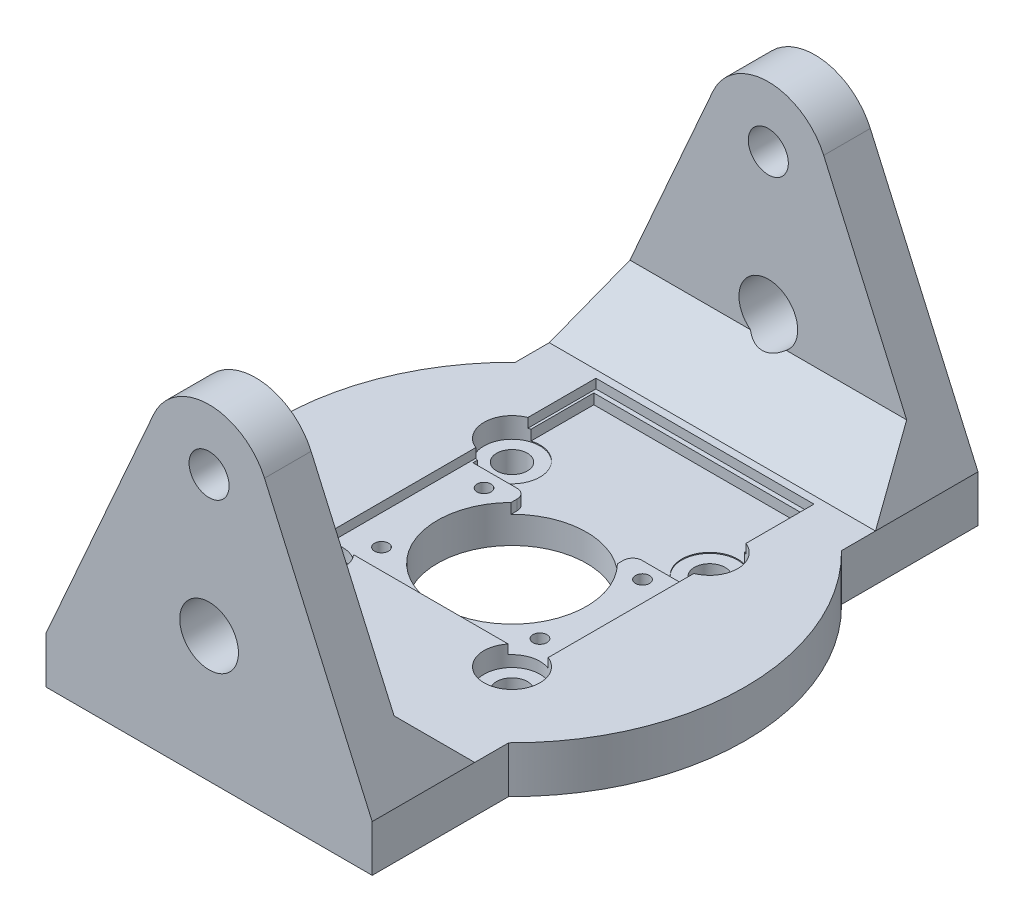
SolidWorks part; units mm, degrees
ref_plane "前视基准面" through (0, 0, 0) normal (0, 0, 1) x (1, 0, 0)
ref_plane "上视基准面" through (0, 0, 0) normal (0, 1, 0) x (1, 0, 0)
ref_plane "右视基准面" through (0, 0, 0) normal (1, 0, 0) x (0, 0, -1)
sketch "草图1" plane through (0, 0, 0) normal (0, 1, 0) x (1, 0, 0)
  line L1 (10.6066, 10.6066) -> (-10.6066, 10.6066) construction
  line L2 (-10.6066, 10.6066) -> (-10.6066, -10.6066) construction
  line L3 (-10.6066, -10.6066) -> (10.6066, -10.6066) construction
  line L4 (10.6066, -10.6066) -> (10.6066, 10.6066) construction
  circle A0 centre (0, 0) radius 25
  circle A1 centre (0, 0) radius 8
  circle A2 centre (0, 0) radius 15 construction
  circle A3 centre (10.6066, 10.6066) radius 1.65
  circle A4 centre (-10.6066, 10.6066) radius 1.65
  circle A5 centre (-10.6066, -10.6066) radius 1.65
  circle A6 centre (10.6066, -10.6066) radius 1.65
  dimension "D1" = 50
  dimension "D2" = 16
  dimension "D3" = 3.3
  dimension "D4" = 30
extrude "凸台-拉伸1" add sketch "草图1" along normal blind 5
sketch "草图5" plane through (0, 5, 0) normal (0, 1, 0) x (1, 0, 0)
  line L0 (11.7, 20.7) -> (-11.7, 20.7)
  line L1 (11, -8) -> (-11, -8) construction
  line L2 (11, -8) -> (11, 20) construction
  line L3 (11, 20) -> (-11, 20) construction
  line L4 (-11, -8) -> (-11, 20) construction
  line L5 (11, -8) -> (-11, 20) construction
  line L6 (11, 20) -> (-11, -8) construction
  line L7 (-11.7, -8.7) -> (-11.7, 20.7)
  line L8 (11.7, -8.7) -> (-11.7, -8.7)
  line L9 (11.7, -8.7) -> (11.7, 20.7)
  line L11 (-8.5, -5.5) -> (8.5, -5.5) construction
  line L12 (-8.5, -5.5) -> (-8.5, 5.5) construction
  line L13 (-8.5, 5.5) -> (8.5, 5.5) construction
  line L14 (8.5, -5.5) -> (8.5, 5.5) construction
  line L15 (-8.5, -5.5) -> (8.5, 5.5) construction
  line L16 (-8.5, 5.5) -> (8.5, -5.5) construction
  point P0 (0, 0)
  point P10 (0, 0)
  dimension "D1" = 22
  dimension "D2" = 28
  dimension "D4" = 17
  dimension "D5" = 11
  dimension "D6" = 2.5
  dimension "D7" = 2.5
  dimension "D3" = 0.7
extrude "切除-拉伸1" cut sketch "草图5" against normal blind 1
sketch "草图6" plane through (0, 5, 0) normal (0, 1, 0) x (1, 0, 0)
  circle A13 centre (-10.6066, 10.6066) radius 3
  circle A14 centre (10.6066, 10.6066) radius 3
  circle A15 centre (10.6066, -10.6066) radius 3
  circle A16 centre (-10.6066, -10.6066) radius 3
  dimension "D1" = 6
extrude "切除-拉伸2" cut sketch "草图6" against normal blind 2.2
sketch "草图9" plane through (0, 4, 0) normal (0, 1, 0) x (1, 0, 0)
  circle A0 centre (-8.5, 5.5) radius 0.75
  circle A1 centre (8.5, 5.5) radius 0.75
  circle A2 centre (8.5, -5.5) radius 0.75
  circle A3 centre (-8.5, -5.5) radius 0.75
  dimension "D1" = 1.5
extrude "切除-拉伸3" cut sketch "草图9" against normal up to next
sketch "草图10" plane through (0, 4, 0) normal (0, 1, 0) x (1, 0, 0)
  line L0 (-5.7008, 5.6126) -> (-5.7008, 6.2466)
  line L1 (-6.7008, 7.2466) -> (-11.4414, 7.2466)
  line L2 (-11.4414, 7.2466) -> (-11.4414, 20.2191)
  line L3 (-11.4414, 20.2191) -> (11.4414, 20.2191)
  line L4 (0, 20.2191) -> (0, 8) construction
  line L5 (11.4414, 7.2466) -> (11.4414, 20.2191)
  line L6 (6.7008, 7.2466) -> (11.4414, 7.2466)
  line L7 (5.7008, 5.6126) -> (5.7008, 6.2466)
  circle A0 centre (0, 0) radius 8 construction
  arc A1 (5.7008, 5.6126) -> (-5.7008, 5.6126) centre (0, 0) ccw
  arc A2 (6.7008, 7.2466) -> (5.7008, 6.2466) centre (6.7008, 6.2466) ccw
  arc A3 (-5.7008, 6.2466) -> (-6.7008, 7.2466) centre (-6.7008, 6.2466) ccw
  point P15 (5.7008, 7.2466)
  point P18 (-5.7008, 7.2466)
  dimension "D1" = 1
extrude "切除-拉伸4" cut sketch "草图10" against normal blind 1.1
sketch "草图12" plane through (0, 0, 0) normal (0, -1, 0) x (1, 0, 0)
  line L0 (17.5, 17.8536) -> (17.5, 32.5)
  line L1 (17.5, -32.5) -> (-17.5, -32.5)
  line L2 (17.5, -32.5) -> (17.5, -17.8536)
  line L3 (17.5, 32.5) -> (-17.5, 32.5)
  line L4 (-17.5, -32.5) -> (-17.5, -17.8536)
  line L5 (17.5, -32.5) -> (-17.5, 32.5) construction
  line L6 (17.5, 32.5) -> (-17.5, -32.5) construction
  line L7 (-17.5, 17.8536) -> (-17.5, 32.5)
  circle A0 centre (0, 0) radius 25 construction
  arc A1 (-17.5, -17.8536) -> (17.5, -17.8536) centre (0, 0) ccw
  arc A2 (17.5, 17.8536) -> (-17.5, 17.8536) centre (0, 0) ccw
  point P0 (0, 0)
  dimension "D1" = 35
  dimension "D2" = 65
extrude "凸台-拉伸3" add sketch "草图12" against normal up to surface (5 mm away) up to face at (0, 5, -4.0294)
sketch "草图13" plane through (0, 5, 0) normal (0, 1, 0) x (1, 0, 0)
  line L0 (17.5, 32.5) -> (17.5, 17.8536) construction
  line L1 (-17.5, 32.5) -> (17.5, 32.5)
  line L2 (-17.5, 32.5) -> (-17.5, 27.5)
  line L3 (-17.5, 27.5) -> (17.5, 27.5)
  line L4 (17.5, 32.5) -> (17.5, 27.5)
  line L5 (-17.5, -32.5) -> (-17.5, -17.8536) construction
  line L6 (17.5, -32.5) -> (-17.5, -32.5)
  line L7 (17.5, -32.5) -> (17.5, -27.5)
  line L8 (17.5, -27.5) -> (-17.5, -27.5)
  line L9 (-17.5, -32.5) -> (-17.5, -27.5)
  dimension "D1" = 5
extrude "凸台-拉伸4" add sketch "草图13" along normal blind 30
chamfer "倒角1" distance 6 angle 45 2 edges at (0, 5, 27.5) (0, 5, -27.5)
sketch "草图14" plane through (0, 0, 32.5) normal (0, 0, 1) x (1, 0, 0)
  line L0 (-17.5, 5) -> (-5.9446, 31.129)
  line L1 (17.5, 5) -> (5.9446, 31.129)
  line L2 (-17.5, 35) -> (17.5, 35) construction
  line L3 (-17.5, 5) -> (-17.5, 35)
  line L4 (-17.5, 35) -> (17.5, 35)
  line L5 (17.5, 35) -> (17.5, 5)
  line L6 (0, 35) -> (0, 0) construction
  line L7 (17.5, 0) -> (-17.5, 0) construction
  arc A0 (-5.9446, 31.129) -> (5.9446, 31.129) centre (0, 28.5) cw
  circle A2 centre (0, 13.5) radius 3.15
  circle A3 centre (0, 28.5) radius 2.15
  line M3 (17.5, 0) -> (17.5, 35)
  line M4 (17.5, 35) -> (-17.5, 35)
  line M5 (-17.5, 35) -> (-17.5, 0)
  dimension "D1" = 6.5
  dimension "D2" = 6.3
  dimension "D4" = 4.3
  dimension "D3" = 15
extrude "切除-拉伸5" cut sketch "草图14" against normal through all contours L0 A0 L4 M5 | A0 L1 M4 M3 | A3 | A2 region at (-12.9325, 25.1419, 32.5) region at (12.9325, 25.1419, 32.5)
